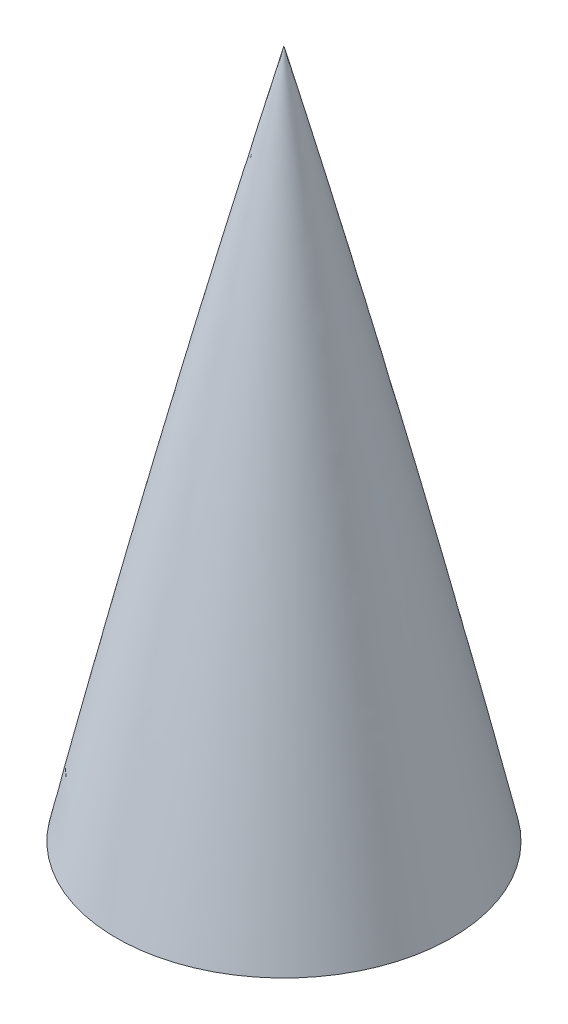
SolidWorks part; units mm, degrees
material "6061-T6 (SS)"
ref_plane "Front Plane" through (0, 0, 0) normal (0, 0, 1) x (1, 0, 0)
ref_plane "Top Plane" through (0, 0, 0) normal (0, 1, 0) x (1, 0, 0)
ref_plane "Right Plane" through (0, 0, 0) normal (1, 0, 0) x (0, 0, -1)
sketch "Sketch1" plane through (0, 0, 0) normal (0, 0, 1) x (1, 0, 0)
  line L0 (0, 0) -> (0, 76.2)
  line L1 (0, 0) -> (18.5515, 0)
  arc A0 (0, 76.2) -> (66.04, -431.8) centre (-1920.8262, -431.8) cw construction
  arc A1 (0, 76.2) -> (18.5515, 0) centre (-1920.8262, -431.8) cw
  dimension "D1" = 508
  dimension "D2" = 66.04
  dimension "D3" = 76.2
revolve "Revolve1" add sketch "Sketch1" angle 360 about L0
ref_axis "Axis1" through (0, 76.2, 0) along (0, -1, 0)
